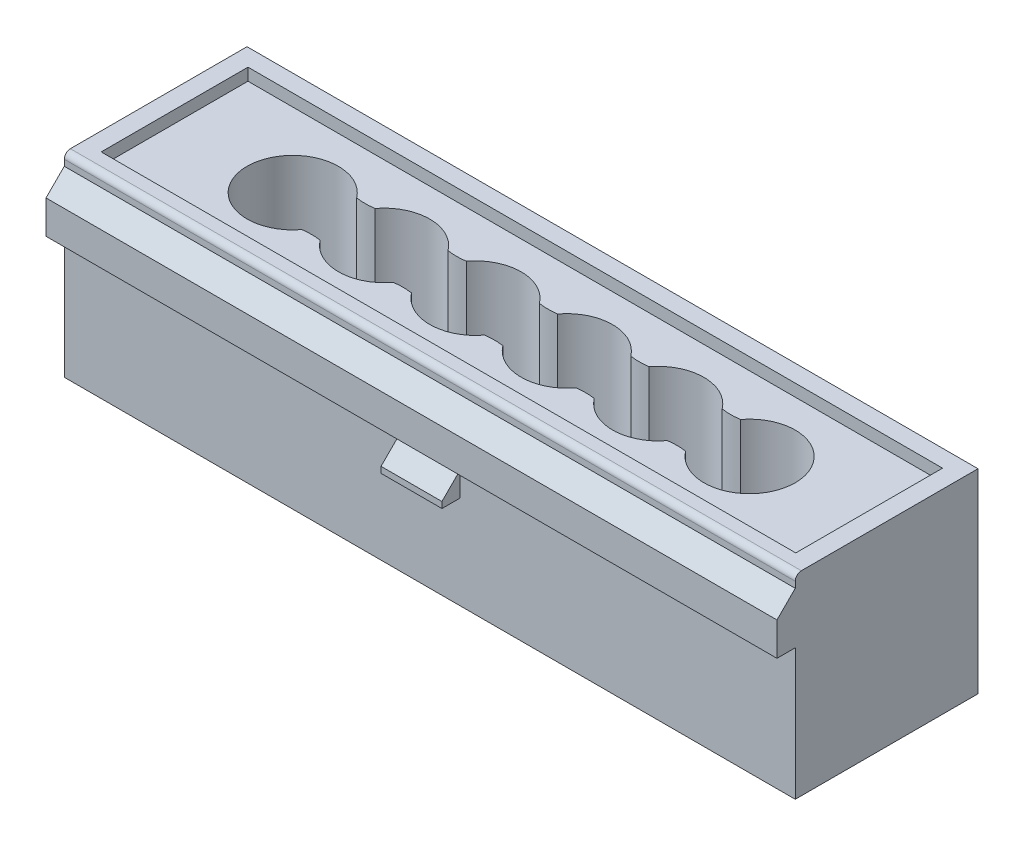
SolidWorks part; units mm, degrees
ref_plane "Front Plane" through (0, 0, 0) normal (0, 0, 1) x (1, 0, 0)
ref_plane "Top Plane" through (0, 0, 0) normal (0, 1, 0) x (1, 0, 0)
ref_plane "Right Plane" through (0, 0, 0) normal (1, 0, 0) x (0, 0, -1)
sketch "Sketch1" plane through (0, 0, 0) normal (0, 1, 0) x (1, 0, 0)
  line L0 (-6, -1.5) -> (-6, 1.5)
  line L1 (-6, 1.5) -> (6, 1.5)
  line L2 (6, 1.5) -> (6, -1.5)
  line L3 (6, -1.5) -> (-6, -1.5)
  arc A0 (0.15, -0.45) -> (1.35, -0.45) centre (0.75, 0) ccw
  arc A1 (-1.35, -0.45) -> (-0.15, -0.45) centre (-0.75, 0) ccw
  arc A2 (-2.85, -0.45) -> (-1.65, -0.45) centre (-2.25, 0) ccw
  arc A3 (1.65, -0.45) -> (2.85, -0.45) centre (2.25, 0) ccw
  arc A4 (3.15, -0.45) -> (3.15, 0.45) centre (3.75, 0) ccw
  arc A5 (-3.15, 0.45) -> (-3.15, -0.45) centre (-3.75, 0) ccw
  arc A6 (-3.15, 0.45) -> (-2.85, 0.45) centre (-3, 1.5) ccw
  arc A7 (-1.65, 0.45) -> (-1.35, 0.45) centre (-1.5, 1.5) ccw
  arc A8 (0.15, 0.45) -> (-0.15, 0.45) centre (0, 1.5) cw
  arc A9 (1.65, 0.45) -> (1.35, 0.45) centre (1.5, 1.5) cw
  arc A10 (2.85, 0.45) -> (3.15, 0.45) centre (3, 1.5) ccw
  arc A11 (3.15, -0.45) -> (2.85, -0.45) centre (3, -1.5) ccw
  arc A12 (1.65, -0.45) -> (1.35, -0.45) centre (1.5, -1.5) ccw
  arc A13 (0.15, -0.45) -> (-0.15, -0.45) centre (0, -1.5) ccw
  arc A14 (-1.35, -0.45) -> (-1.65, -0.45) centre (-1.5, -1.5) ccw
  arc A15 (-2.85, -0.45) -> (-3.15, -0.45) centre (-3, -1.5) ccw
  arc A16 (-1.65, 0.45) -> (-2.85, 0.45) centre (-2.25, 0) ccw
  arc A17 (-0.15, 0.45) -> (-1.35, 0.45) centre (-0.75, 0) ccw
  arc A18 (1.35, 0.45) -> (0.15, 0.45) centre (0.75, 0) ccw
  arc A19 (2.85, 0.45) -> (1.65, 0.45) centre (2.25, 0) ccw
  point P5 (0, 0)
extrude "Boss-Extrude1" add sketch "Sketch1" along normal blind 3
sketch "Sketch2" plane through (0, 0, 1.5) normal (0, 0, 1) x (1, 0, 0)
  line L0 (-6, 3) -> (-6, 2.1543)
  line L1 (-6, 3) -> (-6, 0) construction
  line L2 (-6, 2.1543) -> (6, 2.1543)
  line L3 (6, 3) -> (6, 0) construction
  line L4 (6, 2.1543) -> (6, 3)
  line L5 (6, 3) -> (-6, 3)
  line L6 (0, 1.9341) -> (0.5, 1.9341)
  line L7 (0.5, 1.9341) -> (0.5, 1.5341)
  line L8 (0.5, 1.5341) -> (-0.5, 1.5341)
  line L9 (-0.5, 1.5341) -> (-0.5, 1.9341)
  line L10 (-0.5, 1.9341) -> (0, 1.9341)
extrude "Boss-Extrude2" add sketch "Sketch2" along normal blind 0.3
chamfer "Chamfer1" distance 0.3 angle 45 2 edges at (0, 1.9341, 1.8) (0, 3, 1.8)
sketch "Sketch3" plane through (0, 0, -1.5) normal (0, 0, -1) x (-1, 0, 0)
  line L0 (0, 1.2733) -> (2.9931, 1.2733)
  line L1 (0, 1.2733) -> (-2.9931, 1.2733)
  line L3 (-3.4984, 2.0248) -> (-2.4878, 2.0248)
  line L4 (-3.4984, 2.0248) -> (-3.4984, 0.5217)
  line L5 (-3.4984, 0.5217) -> (-2.4878, 0.5217)
  line L6 (-2.4878, 2.0248) -> (-2.4878, 0.5217)
  line L7 (-3.4984, 2.0248) -> (-2.4878, 0.5217) construction
  line L8 (-3.4984, 0.5217) -> (-2.4878, 2.0248) construction
  line L9 (3.4855, 2.0248) -> (2.5007, 2.0248)
  line L10 (3.4855, 2.0248) -> (3.4855, 0.5217)
  line L11 (3.4855, 0.5217) -> (2.5007, 0.5217)
  line L12 (2.5007, 2.0248) -> (2.5007, 0.5217)
  line L13 (3.4855, 2.0248) -> (2.5007, 0.5217) construction
  line L14 (3.4855, 0.5217) -> (2.5007, 2.0248) construction
  line L15 (-0.5053, 2.0248) -> (0.5053, 2.0248)
  line L16 (-0.5053, 2.0248) -> (-0.5053, 0.5217)
  line L17 (-0.5053, 0.5217) -> (0.5053, 0.5217)
  line L18 (0.5053, 2.0248) -> (0.5053, 0.5217)
  line L19 (-0.5053, 2.0248) -> (0.5053, 0.5217) construction
  line L20 (-0.5053, 0.5217) -> (0.5053, 2.0248) construction
extrude "Cut-Extrude1" cut sketch "Sketch3" against normal blind 0.1 contours L6 L3 L4 L5 | L18 L15 L16 L1 L0 | L9 L12 L11 L10 | L18 L0 L1 L16 L17 region at (0, 1.649, -1.5) region at (0, 0.8975, -1.5) region at (-2.5187, 1.649, -1.5) region at (2.5059, 0.8975, -1.5)
sketch "Sketch4" plane through (0, 3, 0) normal (0, 1, 0) x (1, 0, 0)
  line L0 (-6, 1.5) -> (-6, -1.5)
  line L1 (-6, -1.5) -> (6, -1.5)
  line L2 (6, -1.5) -> (6, 1.5)
  line L3 (6, 1.5) -> (-6, 1.5)
  line L4 (-6, 1.5) -> (-5.7011, 1.5)
  line L5 (-5.7011, 1.217) -> (-5.7011, -1.193)
  line L6 (-5.7011, -1.193) -> (5.7011, -1.193)
  line L7 (5.7011, -1.193) -> (5.7011, 1.217)
  line L8 (5.7011, 1.217) -> (-5.7011, 1.217)
  line M5 (-6, 1.5) -> (-6, -1.5)
  line M6 (-6, -1.5) -> (6, -1.5)
  line M7 (6, -1.5) -> (6, 1.5)
  line M8 (6, 1.5) -> (-6, 1.5)
extrude "Boss-Extrude3" add sketch "Sketch4" along normal blind 0.2 contours L3 L8 L7 L6 L5 M8 M5 M6 M7 region at (-5.8506, 3, -1.3763)
fillet "Fillet1" radius 0.1 1 edges at (0, 3.2, 1.5)
extrude "Boss-Extrude4" add sketch "Sketch1<2>" along normal blind 0.2 contours L3 L2 L1 L0 A19 A10 A4 A11 A3 A12 A0 A13 A1 A14 A2 A15 A5 A6 A16 A7 A17 A8 A18 A9 | A10 A19 A9 A18 A8 A17 A7 A16 A6 A5 A15 A2 A14 A1 A13 A0 A12 A3 A11 A4 region at (-5.8763, 0, 0) region at (0, 0, 0)
sketch "Sketch1<2>" plane through (0, 0, 0) normal (0, 1, 0) x (1, 0, 0) same geometry as "Sketch1"
fillet "Fillet2" radius 0.1 10 edges at (0.75, 0.2, -0.75) (4.5, 0.2, 0) (2.25, 0.2, 0.75) (2.25, 0.2, -0.75) (0.75, 0.2, 0.75) (-0.75, 0.2, -0.75) (-2.25, 0.2, -0.75) (-4.5, 0.2, 0) (-2.25, 0.2, 0.75) (-0.75, 0.2, 0.75)
